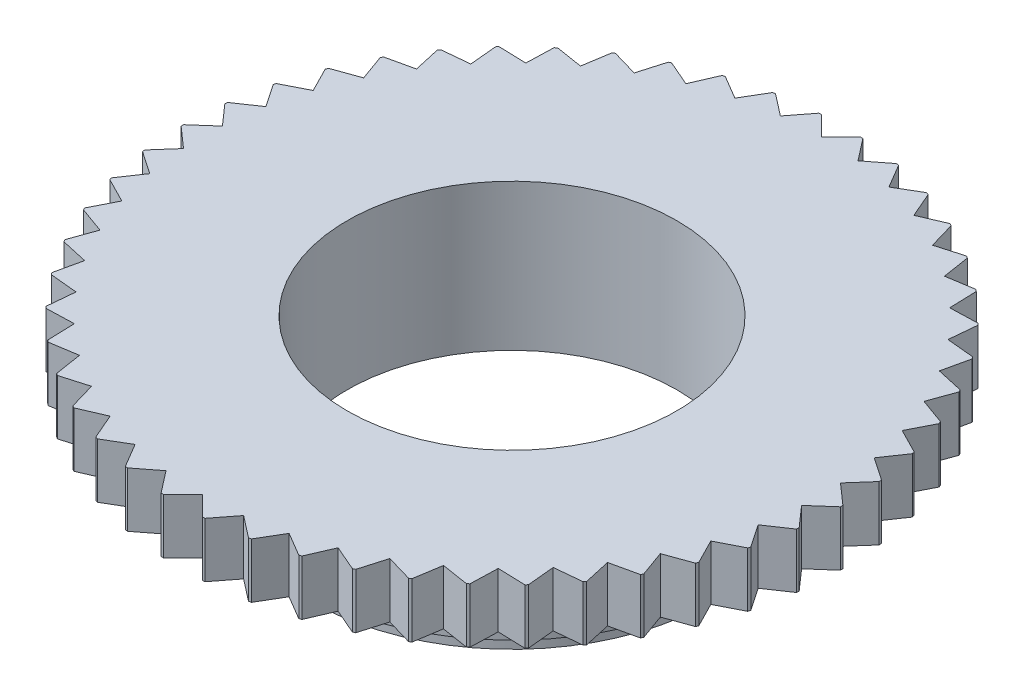
SolidWorks part; units mm, degrees
ref_plane "前视基准面" through (0, 0, 0) normal (0, 0, 1) x (1, 0, 0)
ref_plane "上视基准面" through (0, 0, 0) normal (0, 1, 0) x (1, 0, 0)
ref_plane "右视基准面" through (0, 0, 0) normal (1, 0, 0) x (0, 0, -1)
sketch "Sketch1" plane through (0, 0, 0) normal (0, 1, 0) x (1, 0, 0)
  circle A0 centre (0, 0) radius 18
  circle A1 centre (0, 0) radius 9
extrude "Boss-Extrude1" add sketch "Sketch1" along normal blind 3
sketch "Sketch2" plane through (0, 0, 0) normal (0, -1, 0) x (1, 0, 0)
  circle A0 centre (0, 0) radius 9
  circle A1 centre (0, 0) radius 11.8
extrude "Boss-Extrude2" add sketch "Sketch2" along normal blind 5
thread "Thread1" pitch 1.5 method extrude profile "Thread Profile1" start angle 0, offset 1.5, length 1.5, pitch 1.5, diameter 23.6
ref_plane "Plane1" through (11.8, -3.5, 0) normal (0, 0, -1) x (-1, 0, 0)
sketch "Thread Profile1" plane through (11.8, -3.5, 0) normal (0, 0, -1) x (-1, 0, 0)
  line L0 (0, 0) -> (0, 1.5) construction
  line L11 (0, 0) -> (0, 1.3125)
  line L12 (0, 1.3125) -> (-0.8119, 0.8437)
  line L13 (-0.8119, 0.8437) -> (-0.8119, 0.4687)
  line L15 (-0.8119, 0.4687) -> (0, 0)
  line L17 (-0.8119, 0.6562) -> (0, 0.6562) construction
  point P2 (0, 0)
  dimension "Pitch" = 1.5
  dimension "Profile_Angle" = 60
  dimension "Profile_Land" = 0.375
  dimension "Profile_Height" = 0.8119
sketch "Sketch5" plane through (0, -5, 0) normal (0, -1, 0) x (1, 0, 0)
  circle A1 centre (0, 0) radius 11
  circle A2 centre (0, 0) radius 11.8
extrude "Cut-Extrude1" cut sketch "Sketch5" against normal blind 1
sketch "Sketch8" plane through (0, 3, 0) normal (0, 1, 0) x (1, 0, 0)
  line L0 (0, 0) -> (0, 20.0063) construction
  line L1 (-1.0607, 17.9687) -> (0, 16.9081)
  line L2 (0, 16.9081) -> (1.0607, 17.9687)
  line L3 (2.1191, 16.7747) -> (3.3044, 17.6941)
  line L4 (1.1998, 17.96) -> (2.1191, 16.7747)
  line L5 (4.2049, 16.3769) -> (5.496, 17.1404)
  line L6 (3.4413, 17.668) -> (4.2049, 16.3769)
  line L7 (6.2243, 15.7207) -> (7.6009, 16.3164)
  line L8 (5.6286, 17.0974) -> (6.2243, 15.7207)
  line L9 (8.1455, 14.8166) -> (9.586, 15.2351)
  line L10 (7.727, 16.2571) -> (8.1455, 14.8166)
  line L11 (9.9383, 13.6789) -> (11.4198, 13.9136)
  line L12 (9.7037, 15.1604) -> (9.9383, 13.6789)
  line L13 (11.5744, 12.3254) -> (13.0736, 12.3726)
  line L14 (11.5272, 13.8247) -> (11.5744, 12.3254)
  line L15 (13.0279, 10.7776) -> (14.5212, 10.6364)
  line L16 (13.169, 12.2709) -> (13.0279, 10.7776)
  line L17 (14.2759, 9.0598) -> (15.7398, 8.7326)
  line L18 (14.6032, 10.5237) -> (14.2759, 9.0598)
  line L19 (15.2989, 7.1991) -> (16.7102, 6.691)
  line L20 (15.807, 8.6104) -> (15.2989, 7.1991)
  line L21 (16.0805, 5.2249) -> (17.417, 4.5439)
  line L22 (16.7615, 6.5614) -> (16.0805, 5.2249)
  line L23 (16.6086, 3.1683) -> (17.8492, 2.3251)
  line L24 (17.4517, 4.4089) -> (16.6086, 3.1683)
  line L25 (16.8747, 1.0617) -> (17.9999, 0.0697)
  line L26 (17.8667, 2.1868) -> (16.8747, 1.0617)
  line L27 (16.8747, -1.0617) -> (17.8667, -2.1868)
  line L28 (17.9999, -0.0697) -> (16.8747, -1.0617)
  line L29 (16.6086, -3.1683) -> (17.4517, -4.4089)
  line L30 (17.8492, -2.3251) -> (16.6086, -3.1683)
  line L31 (16.0805, -5.2249) -> (16.7615, -6.5614)
  line L32 (17.417, -4.5439) -> (16.0805, -5.2249)
  line L33 (15.2989, -7.1991) -> (15.807, -8.6104)
  line L34 (16.7102, -6.691) -> (15.2989, -7.1991)
  line L35 (14.2759, -9.0598) -> (14.6032, -10.5237)
  line L36 (15.7398, -8.7326) -> (14.2759, -9.0598)
  line L37 (13.0279, -10.7776) -> (13.169, -12.2709)
  line L38 (14.5212, -10.6364) -> (13.0279, -10.7776)
  line L39 (11.5744, -12.3254) -> (11.5272, -13.8247)
  line L40 (13.0736, -12.3726) -> (11.5744, -12.3254)
  line L41 (9.9383, -13.6789) -> (9.7037, -15.1604)
  line L42 (11.4198, -13.9136) -> (9.9383, -13.6789)
  line L43 (8.1455, -14.8166) -> (7.727, -16.2571)
  line L44 (9.586, -15.2351) -> (8.1455, -14.8166)
  line L45 (6.2243, -15.7207) -> (5.6286, -17.0974)
  line L46 (7.6009, -16.3164) -> (6.2243, -15.7207)
  line L47 (4.2049, -16.3769) -> (3.4413, -17.668)
  line L48 (5.496, -17.1404) -> (4.2049, -16.3769)
  line L49 (2.1191, -16.7747) -> (1.1998, -17.96)
  line L50 (3.3044, -17.6941) -> (2.1191, -16.7747)
  line L51 (0, -16.9081) -> (-1.0607, -17.9687)
  line L52 (1.0607, -17.9687) -> (0, -16.9081)
  line L53 (-2.1191, -16.7747) -> (-3.3044, -17.6941)
  line L54 (-1.1998, -17.96) -> (-2.1191, -16.7747)
  line L55 (-4.2049, -16.3769) -> (-5.496, -17.1404)
  line L56 (-3.4413, -17.668) -> (-4.2049, -16.3769)
  line L57 (-6.2243, -15.7207) -> (-7.6009, -16.3164)
  line L58 (-5.6286, -17.0974) -> (-6.2243, -15.7207)
  line L59 (-8.1455, -14.8166) -> (-9.586, -15.2351)
  line L60 (-7.727, -16.2571) -> (-8.1455, -14.8166)
  line L61 (-9.9383, -13.6789) -> (-11.4198, -13.9136)
  line L62 (-9.7037, -15.1604) -> (-9.9383, -13.6789)
  line L63 (-11.5744, -12.3254) -> (-13.0736, -12.3726)
  line L64 (-11.5272, -13.8247) -> (-11.5744, -12.3254)
  line L65 (-13.0279, -10.7776) -> (-14.5212, -10.6364)
  line L66 (-13.169, -12.2709) -> (-13.0279, -10.7776)
  line L67 (-14.2759, -9.0598) -> (-15.7398, -8.7326)
  line L68 (-14.6032, -10.5237) -> (-14.2759, -9.0598)
  line L69 (-15.2989, -7.1991) -> (-16.7102, -6.691)
  line L70 (-15.807, -8.6104) -> (-15.2989, -7.1991)
  line L71 (-16.0805, -5.2249) -> (-17.417, -4.5439)
  line L72 (-16.7615, -6.5614) -> (-16.0805, -5.2249)
  line L73 (-16.6086, -3.1683) -> (-17.8492, -2.3251)
  line L74 (-17.4517, -4.4089) -> (-16.6086, -3.1683)
  line L75 (-16.8747, -1.0617) -> (-17.9999, -0.0697)
  line L76 (-17.8667, -2.1868) -> (-16.8747, -1.0617)
  line L77 (-16.8747, 1.0617) -> (-17.8667, 2.1868)
  line L78 (-17.9999, 0.0697) -> (-16.8747, 1.0617)
  line L79 (-16.6086, 3.1683) -> (-17.4517, 4.4089)
  line L80 (-17.8492, 2.3251) -> (-16.6086, 3.1683)
  line L81 (-16.0805, 5.2249) -> (-16.7615, 6.5614)
  line L82 (-17.417, 4.5439) -> (-16.0805, 5.2249)
  line L83 (-15.2989, 7.1991) -> (-15.807, 8.6104)
  line L84 (-16.7102, 6.691) -> (-15.2989, 7.1991)
  line L85 (-14.2759, 9.0598) -> (-14.6032, 10.5237)
  line L86 (-15.7398, 8.7326) -> (-14.2759, 9.0598)
  line L87 (-13.0279, 10.7776) -> (-13.169, 12.2709)
  line L88 (-14.5212, 10.6364) -> (-13.0279, 10.7776)
  line L89 (-11.5744, 12.3254) -> (-11.5272, 13.8247)
  line L90 (-13.0736, 12.3726) -> (-11.5744, 12.3254)
  line L91 (-9.9383, 13.6789) -> (-9.7037, 15.1604)
  line L92 (-11.4198, 13.9136) -> (-9.9383, 13.6789)
  line L93 (-8.1455, 14.8166) -> (-7.727, 16.2571)
  line L94 (-9.586, 15.2351) -> (-8.1455, 14.8166)
  line L95 (-6.2243, 15.7207) -> (-5.6286, 17.0974)
  line L96 (-7.6009, 16.3164) -> (-6.2243, 15.7207)
  line L97 (-4.2049, 16.3769) -> (-3.4413, 17.668)
  line L98 (-5.496, 17.1404) -> (-4.2049, 16.3769)
  line L99 (-2.1191, 16.7747) -> (-1.1998, 17.96)
  line L100 (-3.3044, 17.6941) -> (-2.1191, 16.7747)
  circle A0 centre (0, 0) radius 18 construction
  arc A1 (-1.0607, 17.9687) -> (1.0607, 17.9687) centre (0, 0) cw
  arc A2 (1.1998, 17.96) -> (3.3044, 17.6941) centre (0, 0) cw
  arc A3 (3.4413, 17.668) -> (5.496, 17.1404) centre (0, 0) cw
  arc A4 (5.6286, 17.0974) -> (7.6009, 16.3164) centre (0, 0) cw
  arc A5 (7.727, 16.2571) -> (9.586, 15.2351) centre (0, 0) cw
  arc A6 (9.7037, 15.1604) -> (11.4198, 13.9136) centre (0, 0) cw
  arc A7 (11.5272, 13.8247) -> (13.0736, 12.3726) centre (0, 0) cw
  arc A8 (13.169, 12.2709) -> (14.5212, 10.6364) centre (0, 0) cw
  arc A9 (14.6032, 10.5237) -> (15.7398, 8.7326) centre (0, 0) cw
  arc A10 (15.807, 8.6104) -> (16.7102, 6.691) centre (0, 0) cw
  arc A11 (16.7615, 6.5614) -> (17.417, 4.5439) centre (0, 0) cw
  arc A12 (17.4517, 4.4089) -> (17.8492, 2.3251) centre (0, 0) cw
  arc A13 (17.8667, 2.1868) -> (17.9999, 0.0697) centre (0, 0) cw
  arc A14 (17.9999, -0.0697) -> (17.8667, -2.1868) centre (0, 0) cw
  arc A15 (17.8492, -2.3251) -> (17.4517, -4.4089) centre (0, 0) cw
  arc A16 (17.417, -4.5439) -> (16.7615, -6.5614) centre (0, 0) cw
  arc A17 (16.7102, -6.691) -> (15.807, -8.6104) centre (0, 0) cw
  arc A18 (15.7398, -8.7326) -> (14.6032, -10.5237) centre (0, 0) cw
  arc A19 (14.5212, -10.6364) -> (13.169, -12.2709) centre (0, 0) cw
  arc A20 (13.0736, -12.3726) -> (11.5272, -13.8247) centre (0, 0) cw
  arc A21 (11.4198, -13.9136) -> (9.7037, -15.1604) centre (0, 0) cw
  arc A22 (9.586, -15.2351) -> (7.727, -16.2571) centre (0, 0) cw
  arc A23 (7.6009, -16.3164) -> (5.6286, -17.0974) centre (0, 0) cw
  arc A24 (5.496, -17.1404) -> (3.4413, -17.668) centre (0, 0) cw
  arc A25 (3.3044, -17.6941) -> (1.1998, -17.96) centre (0, 0) cw
  arc A26 (1.0607, -17.9687) -> (-1.0607, -17.9687) centre (0, 0) cw
  arc A27 (-1.1998, -17.96) -> (-3.3044, -17.6941) centre (0, 0) cw
  arc A28 (-3.4413, -17.668) -> (-5.496, -17.1404) centre (0, 0) cw
  arc A29 (-5.6286, -17.0974) -> (-7.6009, -16.3164) centre (0, 0) cw
  arc A30 (-7.727, -16.2571) -> (-9.586, -15.2351) centre (0, 0) cw
  arc A31 (-9.7037, -15.1604) -> (-11.4198, -13.9136) centre (0, 0) cw
  arc A32 (-11.5272, -13.8247) -> (-13.0736, -12.3726) centre (0, 0) cw
  arc A33 (-13.169, -12.2709) -> (-14.5212, -10.6364) centre (0, 0) cw
  arc A34 (-14.6032, -10.5237) -> (-15.7398, -8.7326) centre (0, 0) cw
  arc A35 (-15.807, -8.6104) -> (-16.7102, -6.691) centre (0, 0) cw
  arc A36 (-16.7615, -6.5614) -> (-17.417, -4.5439) centre (0, 0) cw
  arc A37 (-17.4517, -4.4089) -> (-17.8492, -2.3251) centre (0, 0) cw
  arc A38 (-17.8667, -2.1868) -> (-17.9999, -0.0697) centre (0, 0) cw
  arc A39 (-17.9999, 0.0697) -> (-17.8667, 2.1868) centre (0, 0) cw
  arc A40 (-17.8492, 2.3251) -> (-17.4517, 4.4089) centre (0, 0) cw
  arc A41 (-17.417, 4.5439) -> (-16.7615, 6.5614) centre (0, 0) cw
  arc A42 (-16.7102, 6.691) -> (-15.807, 8.6104) centre (0, 0) cw
  arc A43 (-15.7398, 8.7326) -> (-14.6032, 10.5237) centre (0, 0) cw
  arc A44 (-14.5212, 10.6364) -> (-13.169, 12.2709) centre (0, 0) cw
  arc A45 (-13.0736, 12.3726) -> (-11.5272, 13.8247) centre (0, 0) cw
  arc A46 (-11.4198, 13.9136) -> (-9.7037, 15.1604) centre (0, 0) cw
  arc A47 (-9.586, 15.2351) -> (-7.727, 16.2571) centre (0, 0) cw
  arc A48 (-7.6009, 16.3164) -> (-5.6286, 17.0974) centre (0, 0) cw
  arc A49 (-5.496, 17.1404) -> (-3.4413, 17.668) centre (0, 0) cw
  arc A50 (-3.3044, 17.6941) -> (-1.1998, 17.96) centre (0, 0) cw
  point P158 (0, 0)
  dimension "D1" = 45
  dimension "D2" = 50
extrude "Cut-Extrude3" cut sketch "Sketch8" against normal blind 3
